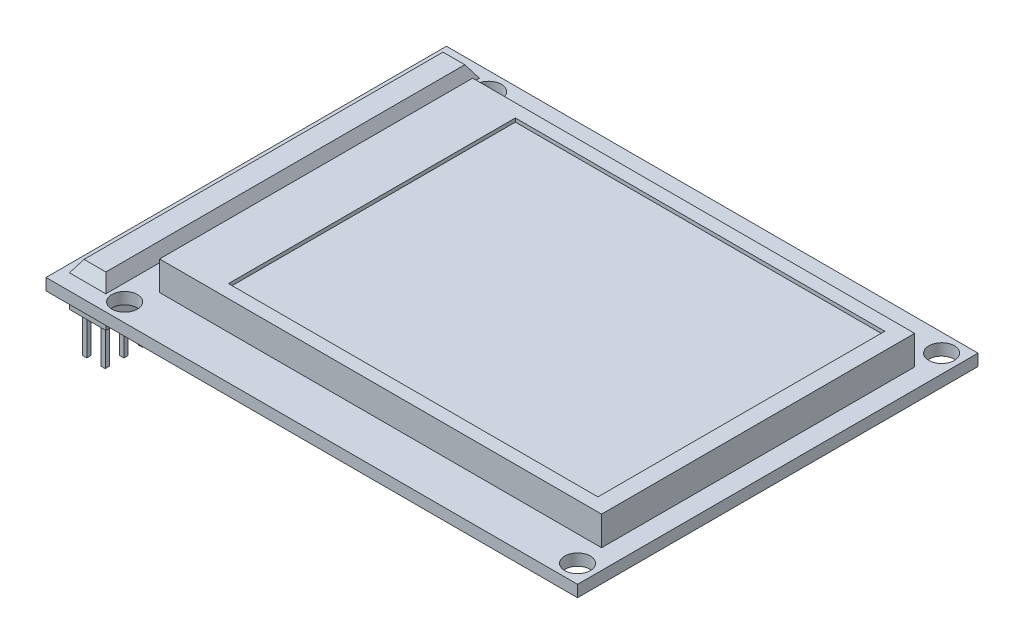
SolidWorks part; units mm, degrees
ref_plane "Front Plane" through (0, 0, 0) normal (0, 0, 1) x (1, 0, 0)
ref_plane "Top Plane" through (0, 0, 0) normal (0, 1, 0) x (1, 0, 0)
ref_plane "Right Plane" through (0, 0, 0) normal (1, 0, 0) x (0, 0, -1)
sketch "Sketch1" plane through (0, 0, 0) normal (0, 1, 0) x (1, 0, 0)
  line L1 (0, 0) -> (73, 0)
  line L2 (0, 0) -> (0, 55)
  line L3 (0, 55) -> (73, 55)
  line L4 (73, 0) -> (73, 55)
  dimension "D1" = 73
  dimension "D2" = 55
extrude "Boss-Extrude1" add sketch "Sketch1" along normal blind 1.6
sketch "Sketch2" plane through (0, 1.6, 0) normal (0, 1, 0) x (1, 0, 0)
  line L0 (73, 0) -> (73, 55) construction
  line L1 (9.6, 6) -> (70.3, 6)
  line L2 (9.6, 6) -> (9.6, 49)
  line L3 (9.6, 49) -> (70.3, 49)
  line L4 (70.3, 6) -> (70.3, 49)
  line L5 (0, 0) -> (73, 0) construction
  line L6 (73, 55) -> (0, 55) construction
  line L7 (0, 55) -> (0, 0) construction
  dimension "D1" = 2.7
  dimension "D2" = 6
  dimension "D3" = 6
  dimension "D4" = 9.6
extrude "Boss-Extrude2" add sketch "Sketch2" along normal blind 4
sketch "Sketch3" plane through (0, 0, 0) normal (0, -1, 0) x (1, 0, 0)
  line L0 (0, 0) -> (73, 0) construction
  line L1 (0, -55) -> (7, -55) construction
  line L2 (0, -55) -> (0, 0) construction
  line L3 (0, 0) -> (7, 0) construction
  line L4 (7, -55) -> (7, 0) construction
  line L5 (2.23, -55) -> (2.23, 0) construction
  line L6 (4.77, 0) -> (4.77, -55) construction
  line L7 (4.77, -52.069) -> (2.23, -52.069) construction
  line L8 (6.06, -2.16) -> (1.06, -2.16)
  line L9 (6.06, -2.16) -> (6.06, -53.46)
  line L10 (6.06, -53.46) -> (1.06, -53.46)
  line L11 (1.06, -2.16) -> (1.06, -53.46)
  line L12 (5.095, -52.394) -> (4.445, -52.394) construction
  line L13 (5.095, -52.394) -> (5.095, -51.744) construction
  line L14 (5.095, -51.744) -> (4.445, -51.744) construction
  line L15 (4.445, -52.394) -> (4.445, -51.744) construction
  line L16 (5.095, -52.394) -> (4.445, -51.744) construction
  line L17 (5.095, -51.744) -> (4.445, -52.394) construction
  line L18 (1.905, -52.394) -> (2.555, -52.394) construction
  line L19 (1.905, -52.394) -> (1.905, -51.744) construction
  line L20 (1.905, -51.744) -> (2.555, -51.744) construction
  line L21 (2.555, -52.394) -> (2.555, -51.744) construction
  line L22 (1.905, -52.394) -> (2.555, -51.744) construction
  line L23 (1.905, -51.744) -> (2.555, -52.394) construction
  point P15 (4.77, -52.069)
  point P20 (2.23, -52.069)
  dimension "D2" = 2.54
  dimension "D3" = 2.23
  dimension "D4" = 51.3
  dimension "D5" = 2.16
  dimension "D6" = 1.06
  dimension "D7" = 5
  dimension "D8" = 0.65
extrude "Boss-Extrude3" add sketch "Sketch3" along normal blind 2.75
sketch "Sketch4" plane through (0, -2.75, 0) normal (0, -1, 0) x (1, 0, 0)
  line L0 (2.23, -55) -> (2.23, 0) construction
  line L2 (4.77, 0) -> (4.77, -55) construction
  line L3 (7, -55) -> (7, 0) construction
  line L4 (2.53, -26.53) -> (1.93, -26.53)
  line L5 (2.53, -26.53) -> (2.53, -25.93)
  line L6 (2.53, -25.93) -> (1.93, -25.93)
  line L7 (1.93, -26.53) -> (1.93, -25.93)
  line L8 (2.53, -26.53) -> (1.93, -25.93) construction
  line L9 (2.53, -25.93) -> (1.93, -26.53) construction
  line L10 (0, -55) -> (0, 0) construction
  line L11 (2.23, -55) -> (2.23, 0) construction
  line L12 (4.77, 0) -> (4.77, -55) construction
  line L13 (7, -55) -> (7, 0) construction
  line L14 (0, -55) -> (0, 0) construction
  line L15 (7, -27.5) -> (0, -27.5) construction
  line L16 (7, -26.23) -> (0, -26.23) construction
  line L17 (6.3052, -26.23) -> (6.3052, -28.77) construction
  line L18 (7, -28.77) -> (0, -28.77) construction
  line L19 (2.53, -25.93) -> (4.47, -25.93) construction
  line L20 (4.47, -25.93) -> (5.07, -25.93)
  line L21 (5.07, -25.93) -> (5.07, -26.53)
  line L22 (5.07, -26.53) -> (4.47, -26.53)
  line L23 (4.47, -26.53) -> (4.47, -25.93)
  line L24 (4.47, -25.93) -> (5.07, -26.53) construction
  line L25 (5.07, -25.93) -> (4.47, -26.53) construction
  line L26 (2.53, -23.99) -> (1.93, -23.99)
  line L27 (1.93, -23.99) -> (1.93, -23.39)
  line L28 (2.53, -23.39) -> (1.93, -23.39)
  line L29 (2.53, -23.99) -> (2.53, -23.39)
  line L30 (4.47, -23.99) -> (4.47, -23.39)
  line L31 (4.47, -23.39) -> (5.07, -23.39)
  line L32 (5.07, -23.39) -> (5.07, -23.99)
  line L33 (5.07, -23.99) -> (4.47, -23.99)
  line L34 (2.53, -21.45) -> (1.93, -21.45)
  line L35 (1.93, -21.45) -> (1.93, -20.85)
  line L36 (2.53, -20.85) -> (1.93, -20.85)
  line L37 (2.53, -21.45) -> (2.53, -20.85)
  line L38 (4.47, -21.45) -> (4.47, -20.85)
  line L39 (4.47, -20.85) -> (5.07, -20.85)
  line L40 (5.07, -20.85) -> (5.07, -21.45)
  line L41 (5.07, -21.45) -> (4.47, -21.45)
  line L42 (2.53, -18.91) -> (1.93, -18.91)
  line L43 (1.93, -18.91) -> (1.93, -18.31)
  line L44 (2.53, -18.31) -> (1.93, -18.31)
  line L45 (2.53, -18.91) -> (2.53, -18.31)
  line L46 (4.47, -18.91) -> (4.47, -18.31)
  line L47 (4.47, -18.31) -> (5.07, -18.31)
  line L48 (5.07, -18.31) -> (5.07, -18.91)
  line L49 (5.07, -18.91) -> (4.47, -18.91)
  line L50 (2.53, -16.37) -> (1.93, -16.37)
  line L51 (1.93, -16.37) -> (1.93, -15.77)
  line L52 (2.53, -15.77) -> (1.93, -15.77)
  line L53 (2.53, -16.37) -> (2.53, -15.77)
  line L54 (4.47, -16.37) -> (4.47, -15.77)
  line L55 (4.47, -15.77) -> (5.07, -15.77)
  line L56 (5.07, -15.77) -> (5.07, -16.37)
  line L57 (5.07, -16.37) -> (4.47, -16.37)
  line L58 (2.53, -13.83) -> (1.93, -13.83)
  line L59 (1.93, -13.83) -> (1.93, -13.23)
  line L60 (2.53, -13.23) -> (1.93, -13.23)
  line L61 (2.53, -13.83) -> (2.53, -13.23)
  line L62 (4.47, -13.83) -> (4.47, -13.23)
  line L63 (4.47, -13.23) -> (5.07, -13.23)
  line L64 (5.07, -13.23) -> (5.07, -13.83)
  line L65 (5.07, -13.83) -> (4.47, -13.83)
  line L66 (2.53, -11.29) -> (1.93, -11.29)
  line L67 (1.93, -11.29) -> (1.93, -10.69)
  line L68 (2.53, -10.69) -> (1.93, -10.69)
  line L69 (2.53, -11.29) -> (2.53, -10.69)
  line L70 (4.47, -11.29) -> (4.47, -10.69)
  line L71 (4.47, -10.69) -> (5.07, -10.69)
  line L72 (5.07, -10.69) -> (5.07, -11.29)
  line L73 (5.07, -11.29) -> (4.47, -11.29)
  line L74 (2.53, -8.75) -> (1.93, -8.75)
  line L75 (1.93, -8.75) -> (1.93, -8.15)
  line L76 (2.53, -8.15) -> (1.93, -8.15)
  line L77 (2.53, -8.75) -> (2.53, -8.15)
  line L78 (4.47, -8.75) -> (4.47, -8.15)
  line L79 (4.47, -8.15) -> (5.07, -8.15)
  line L80 (5.07, -8.15) -> (5.07, -8.75)
  line L81 (5.07, -8.75) -> (4.47, -8.75)
  line L82 (2.53, -6.21) -> (1.93, -6.21)
  line L83 (1.93, -6.21) -> (1.93, -5.61)
  line L84 (2.53, -5.61) -> (1.93, -5.61)
  line L85 (2.53, -6.21) -> (2.53, -5.61)
  line L86 (4.47, -6.21) -> (4.47, -5.61)
  line L87 (4.47, -5.61) -> (5.07, -5.61)
  line L88 (5.07, -5.61) -> (5.07, -6.21)
  line L89 (5.07, -6.21) -> (4.47, -6.21)
  line L90 (2.53, -3.67) -> (1.93, -3.67)
  line L91 (1.93, -3.67) -> (1.93, -3.07)
  line L92 (2.53, -3.07) -> (1.93, -3.07)
  line L93 (2.53, -3.67) -> (2.53, -3.07)
  line L94 (4.47, -3.67) -> (4.47, -3.07)
  line L95 (4.47, -3.07) -> (5.07, -3.07)
  line L96 (5.07, -3.07) -> (5.07, -3.67)
  line L97 (5.07, -3.67) -> (4.47, -3.67)
  line L98 (5.07, -29.07) -> (4.47, -28.47) construction
  line L99 (4.47, -29.07) -> (5.07, -28.47) construction
  line L100 (2.53, -29.07) -> (4.47, -29.07) construction
  line L101 (2.53, -29.07) -> (1.93, -28.47) construction
  line L102 (2.53, -28.47) -> (1.93, -29.07) construction
  line L103 (5.07, -51.33) -> (4.47, -51.33)
  line L104 (5.07, -51.93) -> (5.07, -51.33)
  line L105 (4.47, -51.93) -> (5.07, -51.93)
  line L106 (4.47, -51.33) -> (4.47, -51.93)
  line L107 (2.53, -51.33) -> (2.53, -51.93)
  line L108 (2.53, -51.93) -> (1.93, -51.93)
  line L109 (1.93, -51.33) -> (1.93, -51.93)
  line L110 (2.53, -51.33) -> (1.93, -51.33)
  line L111 (5.07, -48.79) -> (4.47, -48.79)
  line L112 (5.07, -49.39) -> (5.07, -48.79)
  line L113 (4.47, -49.39) -> (5.07, -49.39)
  line L114 (4.47, -48.79) -> (4.47, -49.39)
  line L115 (2.53, -48.79) -> (2.53, -49.39)
  line L116 (2.53, -49.39) -> (1.93, -49.39)
  line L117 (1.93, -48.79) -> (1.93, -49.39)
  line L118 (2.53, -48.79) -> (1.93, -48.79)
  line L119 (5.07, -46.25) -> (4.47, -46.25)
  line L120 (5.07, -46.85) -> (5.07, -46.25)
  line L121 (4.47, -46.85) -> (5.07, -46.85)
  line L122 (4.47, -46.25) -> (4.47, -46.85)
  line L123 (2.53, -46.25) -> (2.53, -46.85)
  line L124 (2.53, -46.85) -> (1.93, -46.85)
  line L125 (1.93, -46.25) -> (1.93, -46.85)
  line L126 (2.53, -46.25) -> (1.93, -46.25)
  line L127 (5.07, -43.71) -> (4.47, -43.71)
  line L128 (5.07, -44.31) -> (5.07, -43.71)
  line L129 (4.47, -44.31) -> (5.07, -44.31)
  line L130 (4.47, -43.71) -> (4.47, -44.31)
  line L131 (2.53, -43.71) -> (2.53, -44.31)
  line L132 (2.53, -44.31) -> (1.93, -44.31)
  line L133 (1.93, -43.71) -> (1.93, -44.31)
  line L134 (2.53, -43.71) -> (1.93, -43.71)
  line L135 (5.07, -41.17) -> (4.47, -41.17)
  line L136 (5.07, -41.77) -> (5.07, -41.17)
  line L137 (4.47, -41.77) -> (5.07, -41.77)
  line L138 (4.47, -41.17) -> (4.47, -41.77)
  line L139 (2.53, -41.17) -> (2.53, -41.77)
  line L140 (2.53, -41.77) -> (1.93, -41.77)
  line L141 (1.93, -41.17) -> (1.93, -41.77)
  line L142 (2.53, -41.17) -> (1.93, -41.17)
  line L143 (5.07, -38.63) -> (4.47, -38.63)
  line L144 (5.07, -39.23) -> (5.07, -38.63)
  line L145 (4.47, -39.23) -> (5.07, -39.23)
  line L146 (4.47, -38.63) -> (4.47, -39.23)
  line L147 (2.53, -38.63) -> (2.53, -39.23)
  line L148 (2.53, -39.23) -> (1.93, -39.23)
  line L149 (1.93, -38.63) -> (1.93, -39.23)
  line L150 (2.53, -38.63) -> (1.93, -38.63)
  line L151 (5.07, -36.09) -> (4.47, -36.09)
  line L152 (5.07, -36.69) -> (5.07, -36.09)
  line L153 (4.47, -36.69) -> (5.07, -36.69)
  line L154 (4.47, -36.09) -> (4.47, -36.69)
  line L155 (2.53, -36.09) -> (2.53, -36.69)
  line L156 (2.53, -36.69) -> (1.93, -36.69)
  line L157 (1.93, -36.09) -> (1.93, -36.69)
  line L158 (2.53, -36.09) -> (1.93, -36.09)
  line L159 (5.07, -33.55) -> (4.47, -33.55)
  line L160 (5.07, -34.15) -> (5.07, -33.55)
  line L161 (4.47, -34.15) -> (5.07, -34.15)
  line L162 (4.47, -33.55) -> (4.47, -34.15)
  line L163 (2.53, -33.55) -> (2.53, -34.15)
  line L164 (2.53, -34.15) -> (1.93, -34.15)
  line L165 (1.93, -33.55) -> (1.93, -34.15)
  line L166 (2.53, -33.55) -> (1.93, -33.55)
  line L167 (5.07, -31.01) -> (4.47, -31.01)
  line L168 (5.07, -31.61) -> (5.07, -31.01)
  line L169 (4.47, -31.61) -> (5.07, -31.61)
  line L170 (4.47, -31.01) -> (4.47, -31.61)
  line L171 (2.53, -31.01) -> (2.53, -31.61)
  line L172 (2.53, -31.61) -> (1.93, -31.61)
  line L173 (1.93, -31.01) -> (1.93, -31.61)
  line L174 (2.53, -31.01) -> (1.93, -31.01)
  line L175 (5.07, -28.47) -> (4.47, -28.47)
  line L176 (5.07, -29.07) -> (5.07, -28.47)
  line L177 (4.47, -29.07) -> (5.07, -29.07)
  line L178 (4.47, -28.47) -> (4.47, -29.07)
  line L179 (2.53, -28.47) -> (2.53, -29.07)
  line L180 (2.53, -29.07) -> (1.93, -29.07)
  line L181 (1.93, -28.47) -> (1.93, -29.07)
  line L182 (2.53, -28.47) -> (1.93, -28.47)
  point P21 (2.23, -26.23)
  point P22 (4.77, -26.23)
  point P28 (6.3052, -27.5)
  point P179 (4.77, -28.77)
  point P180 (2.23, -28.77)
  dimension "D1" = 0.6
  dimension "D2" = 2.54
  dimension "D3" = 10
extrude "Boss-Extrude4" add sketch "Sketch4" along normal blind 5.5
sketch "Sketch5" plane through (0, 0, 0) normal (0, -1, 0) x (1, 0, 0)
  line L0 (73, 0) -> (73, -55) construction
  line L1 (66.5, -13) -> (50, -13)
  line L2 (66.5, -13) -> (66.5, -42)
  line L3 (66.5, -42) -> (50, -42)
  line L4 (50, -13) -> (50, -42)
  line L7 (73, -55) -> (0, -55) construction
  line L8 (0, 0) -> (73, 0) construction
  dimension "D1" = 13
  dimension "D2" = 13
  dimension "D3" = 23
  dimension "D4" = 6.5
extrude "Boss-Extrude5" add sketch "Sketch5" along normal blind 3
sketch "Sketch10" plane through (0, 1.6, 0) normal (0, 1, 0) x (1, 0, 0)
  line L0 (70.5, 52.5) -> (8.3, 52.5) construction
  line L1 (8.3, 52.5) -> (8.3, 2.5) construction
  line L2 (8.3, 2.5) -> (70.5, 2.5) construction
  line L3 (70.5, 2.5) -> (70.5, 52.5) construction
  line L4 (73, 55) -> (0, 55) construction
  line L5 (73, 0) -> (73, 55) construction
  line L6 (0, 55) -> (0, 0) construction
  line L7 (0, 0) -> (73, 0) construction
  circle A0 centre (70.5, 52.5) radius 1.75
  circle A1 centre (70.5, 2.5) radius 1.75
  circle A2 centre (8.3, 2.5) radius 1.75
  circle A3 centre (8.3, 52.5) radius 1.75
  dimension "D1" = 3.5
  dimension "D2" = 2.5
  dimension "D3" = 2.5
  dimension "D4" = 8.3
  dimension "D5" = 2.5
extrude "Cut-Extrude3" cut sketch "Sketch10" against normal through all
sketch "Sketch6" plane through (73, 0, 0) normal (1, 0, 0) x (0, 0, -1)
  line L3 (13.05, 0) -> (41.95, 0)
  line L6 (41.95, 0) -> (41.95, -2.95)
  line L7 (41.95, -2.95) -> (13.05, -2.95)
  line L8 (13.05, -2.95) -> (13.05, 0)
  line L9 (41.95, 0) -> (41.95, -2.95)
  line L10 (41.95, -2.95) -> (13.05, -2.95)
  line L11 (13.05, -2.95) -> (13.05, 0)
  dimension "D1" = 0.05
extrude "Cut-Extrude1" cut sketch "Sketch6" against normal blind 30
sketch "Sketch7" plane through (0, 1.6, 0) normal (0, 1, 0) x (1, 0, 0)
  line L4 (6.06, 2.16) -> (6.06, 53.46)
  line L5 (6.06, 2.16) -> (6.06, 53.46)
  line L6 (1.06, 2.16) -> (6.06, 2.16)
  line L7 (1.06, 2.16) -> (6.06, 2.16)
  line L8 (1.06, 53.46) -> (1.06, 2.16)
  line L9 (1.06, 53.46) -> (1.06, 2.16)
  line L10 (6.06, 53.46) -> (1.06, 53.46)
  line L11 (6.06, 53.46) -> (1.06, 53.46)
  dimension "D1" = 0
extrude "Boss-Extrude6" add sketch "Sketch7" along normal blind 1.6 draft 32
sketch "Sketch8" plane through (0, 0, 0) normal (0, -1, 0) x (1, 0, 0)
  line L0 (73, -55) -> (0, -55) construction
  line L1 (45, -40) -> (34, -40)
  line L2 (45, -40) -> (45, -14)
  line L3 (45, -14) -> (34, -14)
  line L4 (34, -40) -> (34, -14)
  line L5 (73, 0) -> (73, -55) construction
  line L6 (73, 0) -> (73, -55) construction
  line L7 (0, 0) -> (73, 0) construction
  line L8 (73, -55) -> (0, -55) construction
  line L9 (22, -44) -> (15, -44)
  line L10 (22, -44) -> (22, -36)
  line L11 (22, -36) -> (15, -36)
  line L12 (15, -44) -> (15, -36)
  dimension "D1" = 15
  dimension "D2" = 39
  dimension "D3" = 28
  dimension "D4" = 14
  dimension "D5" = 51
  dimension "D6" = 11
  dimension "D7" = 58
  dimension "D8" = 19
extrude "Boss-Extrude7" add sketch "Sketch8" along normal blind 1.6 draft 15
sketch "Sketch9" plane through (0, 5.6, 0) normal (0, 1, 0) x (1, 0, 0)
  line L1 (17.26, 47.2) -> (68, 47.2)
  line L2 (17.26, 47.2) -> (17.26, 7.8)
  line L3 (17.26, 7.8) -> (68, 7.8)
  line L4 (68, 47.2) -> (68, 7.8)
  line L7 (73, 55) -> (0, 55) construction
  line L8 (0, 0) -> (73, 0) construction
  line L9 (0, 55) -> (0, 0) construction
  line L10 (73, 0) -> (73, 55) construction
  dimension "D1" = 7.8
  dimension "D2" = 7.8
  dimension "D3" = 39.4
  dimension "D4" = 17.26
  dimension "D5" = 5
extrude "Cut-Extrude2" cut sketch "Sketch9" against normal blind 0.5
sketch "Sketch11" plane through (0, -8.25, 0) normal (0, -1, 0) x (1, 0, 0)
  line L0 (2.53, -51.93) -> (1.93, -51.33) construction
  point P4 (2.23, -51.63)
ref_axis "Axis1" through (2.23, -8.25, -51.63) along (0, -1, 0)
